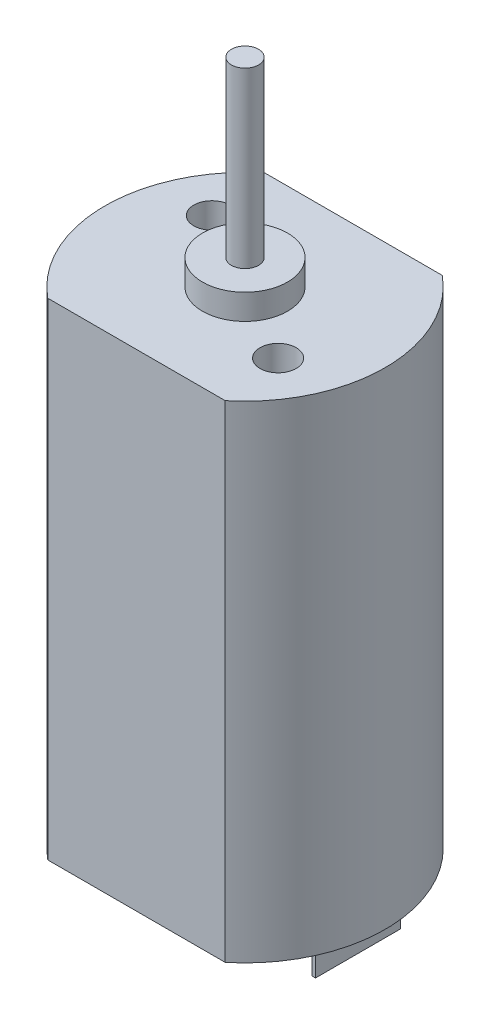
SolidWorks part; units mm, degrees
note: '?' marks a value the reader was unsure of.
ref_plane "Front Plane" through (0, 0, 0) normal (0, 0, 1) x (1, 0, 0)
ref_plane "Top Plane" through (0, 0, 0) normal (0, 1, 0) x (1, 0, 0)
ref_plane "Right Plane" through (0, 0, 0) normal (1, 0, 0) x (0, 0, -1)
sketch "Sketch1" plane through (0, 0, 0) normal (0, 1, 0) x (1, 0, 0)
  line L0 (-4.9054, 6) -> (4.9054, 6)
  line L1 (4.9054, -6) -> (-4.9054, -6)
  arc A0 (-4.9054, 6) -> (-4.9054, -6) centre (0, 0) ccw
  arc A1 (4.9054, -6) -> (4.9054, 6) centre (0, 0) ccw
  dimension "D1" = 7.75
  dimension "D2" = 12
extrude "Boss-Extrude1" add sketch "Sketch1" along normal mid plane 26.9
sketch "Sketch2" plane through (0, 13.45, 0) normal (0, 1, 0) x (1, 0, 0)
  circle A0 centre (0, 0) radius 2.35
  dimension "D1" = 4.7
extrude "Boss-Extrude2" add sketch "Sketch2" along normal blind 1.4
sketch "Sketch3" plane through (0, 14.85, 0) normal (0, 1, 0) x (1, 0, 0)
  circle A0 centre (0, 0) radius 0.75
  dimension "D1" = 1.5
extrude "Boss-Extrude5" add sketch "Sketch3" along normal blind 9.6
sketch "Sketch4" plane through (0, -13.45, 0) normal (0, -1, 0) x (1, 0, 0)
  line L0 (-6.05, 0) -> (6.05, 0) construction
  line L1 (-6.25, 2.35) -> (-6.05, 2.35)
  line L2 (-6.25, 2.35) -> (-6.25, -2.35)
  line L3 (-6.25, -2.35) -> (-6.05, -2.35)
  line L4 (-6.05, 2.35) -> (-6.05, -2.35)
  line L5 (6.05, 2.35) -> (6.25, 2.35)
  line L6 (6.05, 2.35) -> (6.05, -2.35)
  line L7 (6.05, -2.35) -> (6.25, -2.35)
  line L8 (6.25, 2.35) -> (6.25, -2.35)
  dimension "D1" = 0.2
  dimension "D2" = 12.1
  dimension "D3" = 4.7
extrude "Boss-Extrude6" add sketch "Sketch4" along normal blind 1.9
sketch "Sketch5" plane through (0, 13.45, 0) normal (0, 1, 0) x (1, 0, 0)
  line L0 (-4.3301, 2.5) -> (4.3301, -2.5) construction
  line L1 (0, 0) -> (-5.6857, 0) construction
  circle A0 centre (-4.3301, 2.5) radius 1
  circle A1 centre (4.3301, -2.5) radius 1
  dimension "D3" = 2
  dimension "D1" = 30
  dimension "D2" = 10
extrude "Cut-Extrude1" cut sketch "Sketch5" against normal blind 1.9
ref_axis "Axis1" through (0, 15.9889, 0) along (0, -1, 0)?
move or copy body "Body-Move/Copy1" [suppressed] bodies to move or copy 105
